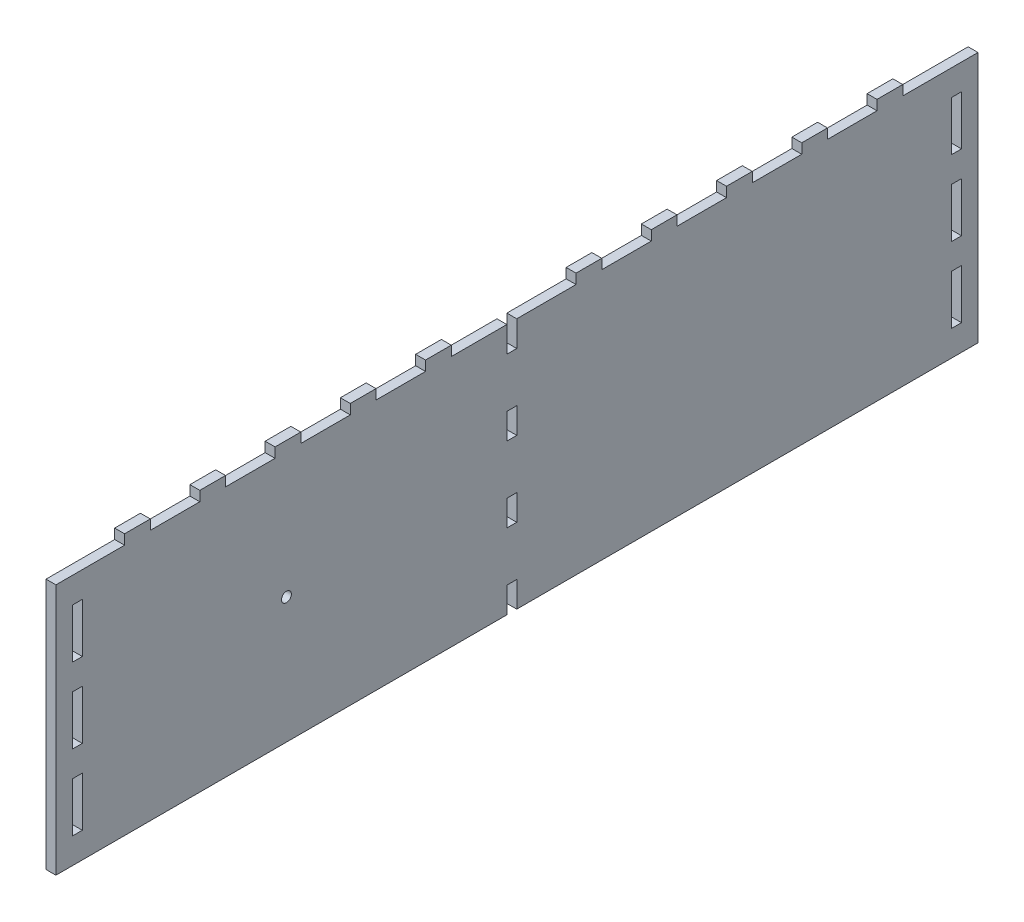
SolidWorks part; units mm, degrees
material "ENPH 253 Hardboard"
ref_plane "Front Plane" through (0, 0, 0) normal (0, 0, 1) x (1, 0, 0)
ref_plane "Top Plane" through (0, 0, 0) normal (0, 1, 0) x (1, 0, 0)
ref_plane "Right Plane" through (0, 0, 0) normal (1, 0, 0) x (0, 0, -1)
sketch "Sketch1" plane through (0, 0, 0) normal (1, 0, 0) x (0, 0, -1)
  line L1 (-139.7, 38.1) -> (139.7, 38.1)
  line L2 (-139.7, 38.1) -> (-139.7, -38.1)
  line L3 (-139.7, -38.1) -> (139.7, -38.1)
  line L4 (139.7, 38.1) -> (139.7, -38.1)
  line L5 (-139.7, 38.1) -> (139.7, -38.1) construction
  line L6 (-139.7, -38.1) -> (139.7, 38.1) construction
  point P0 (0, 0)
  dimension "D1" = 279.4
  dimension "D2" = 76.2
extrude "Boss-Extrude1" add sketch "Sketch1" against normal blind 3 contours L2 L3 L4 L1
sketch "Sketch3" plane through (-3, 0, 0) normal (-1, 0, 0) x (0, 0, 1)
  line L0 (-139.7, 38.1) -> (-139.7, -38.1) construction
  line L1 (139.7, 38.1) -> (139.7, -38.1) construction
  line L2 (139.7, 38.1) -> (-139.7, 38.1) construction
  line L3 (134.7, 30.3) -> (131.7, 30.3)
  line L4 (134.7, 30.3) -> (134.7, 15.3)
  line L5 (134.7, 15.3) -> (131.7, 15.3)
  line L6 (131.7, 30.3) -> (131.7, 15.3)
  line L7 (139.7, 38.1) -> (139.7, -38.1) construction
  circle A0 centre (69.85, 0) radius 50.8 construction
  circle A1 centre (-69.85, 0) radius 50.8 construction
  dimension "D1" = 101.6
  dimension "D2" = 101.6
  dimension "D3" = 69.85
  dimension "D4" = 69.85
  dimension "D5" = 15
  dimension "D6" = 7.8
  dimension "D7" = 5
  dimension "D8" = 3
extrude "Cut-Extrude1" cut sketch "Sketch3" against normal through all
pattern_linear "LPattern1" count 3 spacing 22.8 along (0, -1, 0) of "Cut-Extrude1"
mirror "Mirror1" about plane through (0, 0, 0) normal (0, 0, 1) of "LPattern1"
hole_wizard "Ø3.0mm Clearance Dowel Hole1" positions "Sketch4" profile "Sketch5" hole size "Ø3.0" standard "ANSI Metric" end condition through all
sketch "Sketch4" plane through (-3, 0, 0) normal (-1, 0, 0) x (0, 0, 1)
  point P3 (69.85, 0)
sketch "Sketch5" plane through (-3, 0, 69.85) normal (0, 1, 0) x (0, 0, 1)
  line L0 (0, 0) -> (0, 3)
  line L1 (0, 3) -> (1.5, 3)
  line L2 (1.5, 3) -> (1.5, 0)
  line L5 (1.5, 0) -> (0, 0)
  line L11 (0, -6.35) -> (0, 107.95) construction
  dimension "Thru Hole Dia." = 3
  dimension "Thru Hole Depth" = 3
sketch "Sketch6" plane through (-3, 0, 0) normal (-1, 0, 0) x (0, 0, 1)
  line L0 (139.7, 38.1) -> (-139.7, 38.1) construction
  line L1 (0.06, 38.1) -> (3.06, 38.1)
  line L2 (0.06, 38.1) -> (0.06, 30.3)
  line L3 (0.06, 30.3) -> (3.06, 30.3)
  line L4 (3.06, 38.1) -> (3.06, 30.3)
  dimension "D1" = 136.64
  dimension "D2" = 3
  dimension "D3" = 7.8
extrude "Cut-Extrude2" cut sketch "Sketch6" against normal through all
pattern_linear "LPattern2" count 4 spacing 22.8 along (0, -1, 0) of "Cut-Extrude2"
sketch "Sketch8" plane through (0, 38.1, 0) normal (0, 1, 0) x (1, 0, 0)
  line L0 (0, -139.7) -> (0, -3.06) construction
  line L1 (0, 116.9) -> (-3, 116.9)
  line L2 (0, 116.9) -> (0, 109.1)
  line L3 (0, 109.1) -> (-3, 109.1)
  line L4 (-3, 116.9) -> (-3, 109.1)
  line L5 (-3, -139.7) -> (-3, -3.06) construction
  line L7 (-3, 139.7) -> (0, 139.7) construction
  dimension "D1" = 22.8
  dimension "D2" = 7.8
extrude "Boss-Extrude2" add sketch "Sketch8" along normal blind 3
pattern_linear "LPattern4" count 11 spacing 22.8 along (0, 0, 1) skipping (5, 0) of "Boss-Extrude2"
equation "\"D4@Sketch3\"=\"D3@Sketch3\""
